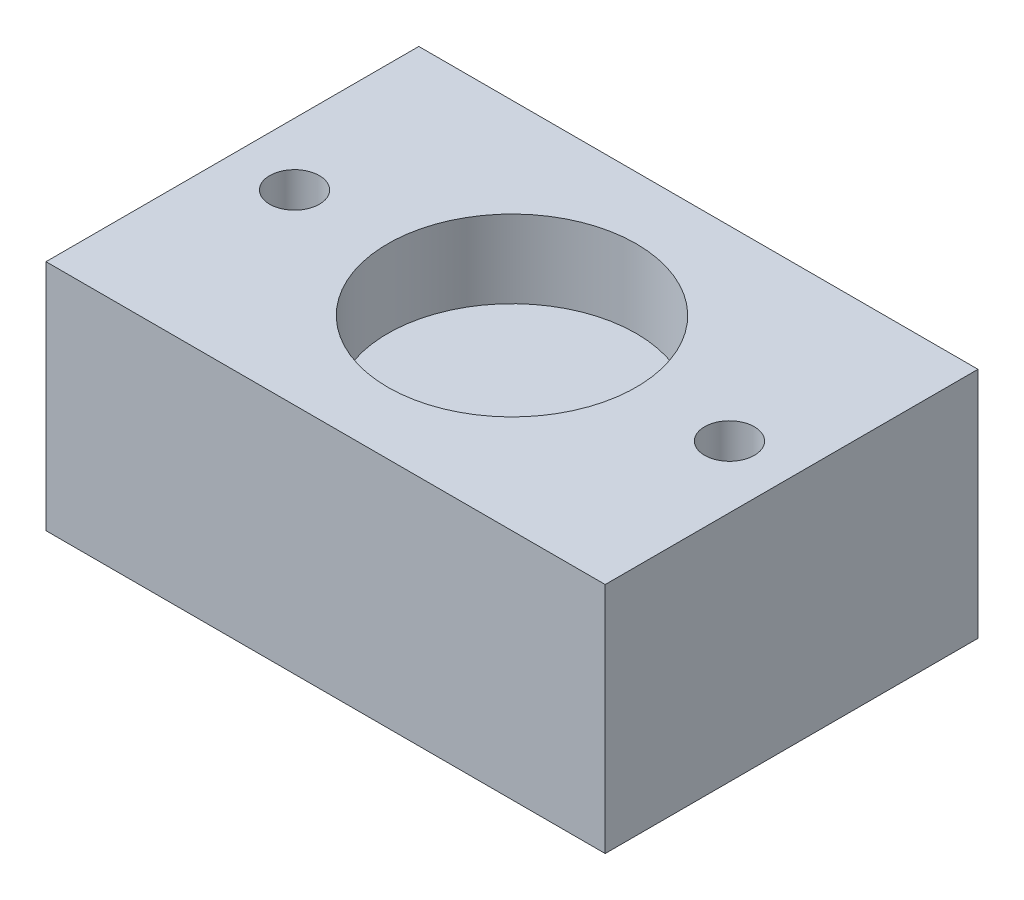
SolidWorks part; units mm, degrees
ref_plane "Front Plane" through (0, 0, 0) normal (0, 0, 1) x (1, 0, 0)
ref_plane "Top Plane" through (0, 0, 0) normal (0, 1, 0) x (1, 0, 0)
ref_plane "Right Plane" through (0, 0, 0) normal (1, 0, 0) x (0, 0, -1)
sketch "Sketch1" plane through (0, 0, 0) normal (0, 1, 0) x (1, 0, 0)
  line L1 (0, 0) -> (36, 0)
  line L2 (0, 0) -> (0, 24)
  line L3 (0, 24) -> (36, 24)
  line L4 (36, 0) -> (36, 24)
  line L5 (0, 0) -> (36, 24) construction
  line L6 (0, 24) -> (36, 0) construction
  point P4 (18, 12)
  dimension "D1" = 24
  dimension "D2" = 36
extrude "Boss-Extrude1" add sketch "Sketch1" along normal blind 15
sketch "Sketch2" plane through (0, 15, 0) normal (0, 1, 0) x (1, 0, 0)
  line L0 (36, 24) -> (0, 24) construction
  line L1 (0, 24) -> (0, 0) construction
  circle A0 centre (18, 12) radius 8
  dimension "D1" = 16
  dimension "D2" = 12
  dimension "D3" = 18
extrude "Cut-Extrude1" cut sketch "Sketch2" against normal blind 5
hole_wizard "Ø3.2 (3.2) Diameter Hole1" positions "Sketch3" profile "Sketch4" hole size "Ø3.2" standard "ANSI Metric" end condition through all
sketch "Sketch3" plane through (0, 15, 0) normal (0, 1, 0) x (1, 0, 0)
  line L0 (36, 0) -> (36, 24) construction
  line L1 (36, 24) -> (0, 24) construction
  line L2 (0, 24) -> (0, 0) construction
  point P0 (4, 12)
  point P2 (32, 12)
  dimension "D1" = 4
  dimension "D2" = 12
  dimension "D3" = 4
  dimension "D4" = 12
sketch "Sketch4" plane through (4, 15, -12) normal (1, 0, 0) x (0, 0, 1)
  line L0 (0, 0) -> (0, 15)
  line L1 (0, 15) -> (1.6, 15)
  line L2 (1.6, 15) -> (1.6, 0)
  line L5 (1.6, 0) -> (0, 0)
  line L11 (0, -6.35) -> (0, 107.95) construction
  dimension "Thru Hole Dia." = 3.2
  dimension "Thru Hole Depth" = 15
